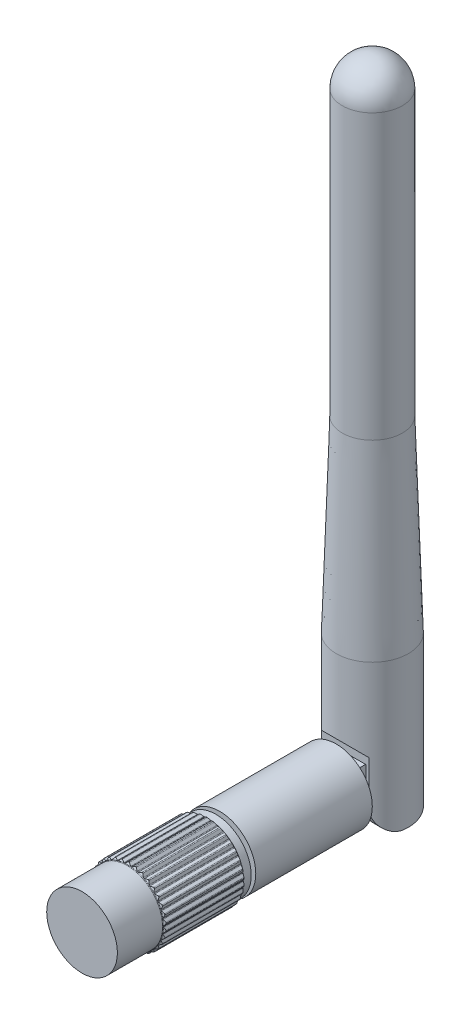
SolidWorks part; units mm, degrees
ref_plane "Front Plane" through (0, 0, 0) normal (0, 0, 1) x (1, 0, 0)
ref_plane "Top Plane" through (0, 0, 0) normal (0, 1, 0) x (1, 0, 0)
ref_plane "Right Plane" through (0, 0, 0) normal (1, 0, 0) x (0, 0, -1)
sketch "Sketch1" plane through (0, 0, 0) normal (1, 0, 0) x (0, 0, -1)
  line L0 (0, 0) -> (4.8, 0)
  line L1 (4.8, 0) -> (4.8, 20)
  line L2 (4.8, 20) -> (4, 45)
  line L3 (4, 45) -> (4, 82.7)
  line L4 (0, 0) -> (0, 86.7)
  line L5 (0, 86.7) -> (7.0365, 86.7) construction
  arc A0 (4, 82.7) -> (0, 86.7) centre (0, 82.7) ccw
  dimension "D1" = 86.7
  dimension "D2" = 4.8
  dimension "D3" = 4
  dimension "D4" = 20
  dimension "D5" = 25
revolve "Revolve1" add sketch "Sketch1" angle 360 about L4
sketch "Sketch2" plane through (0, 0, 0) normal (0, -1, 0) x (1, 0, 0)
  line L1 (-2.75, 4.8) -> (2.75, 4.8)
  line L2 (-2.75, 4.8) -> (-2.75, -3)
  line L3 (-2.75, -3) -> (2.75, -3)
  line L4 (2.75, 4.8) -> (2.75, -3)
  circle A1 centre (0, 0) radius 4.8 construction
  dimension "D1" = 5.5
  dimension "D2" = 3
  dimension "D3" = 2.75
extrude "Cut-Extrude1" cut sketch "Sketch2" against normal blind 8
sketch "Sketch4" plane through (0, 0, 0) normal (1, 0, 0) x (0, 0, -1)
  line L0 (-4.8, 10.2) -> (-3.6, 9)
  line L1 (-4.8, 20) -> (-4.8, 8) construction
  line L2 (-3.6, 9) -> (-3.6, 3)
  line L3 (-3.9341, 0) -> (4.8, 0) construction
  line L4 (-0.6, 0) -> (-4.8, 0)
  line L5 (-4.8, 0) -> (-4.8, 10.2)
  arc A0 (-3.6, 3) -> (-0.6, 0) centre (-0.6, 3) ccw
  dimension "D4" = 3
  dimension "D1" = 45
  dimension "D2" = 1.2
  dimension "D3" = 9
extrude "Cut-Extrude2" cut sketch "Sketch4" against normal up to next and the other way up to next
sketch "Sketch3" plane through (-2.75, 0, 0) normal (1, 0, 0) x (0, 0, -1)
  line L0 (-4.8, 7.7) -> (-4.8, 1.9)
  line L1 (-4.8, 1.9) -> (0, 1.9)
  line L2 (0, 7.7) -> (-4.8, 7.7)
  line L3 (-0.6, 0) -> (4.8, 0) construction
  arc A0 (0, 1.9) -> (0, 7.7) centre (0, 4.8) ccw
  dimension "D1" = 5.8
  dimension "D2" = 4.8
  dimension "D3" = 4.8
extrude "Boss-Extrude1" add sketch "Sketch3" along normal blind 4.8 from offset 0.35 separate body
sketch "Sketch5" plane through (0, 0, 4.8) normal (0, 0, 1) x (1, 0, 0)
  line L0 (2.4, 1.9) -> (-2.4, 1.9) construction
  circle A0 centre (0, 4.8) radius 4.8
  dimension "D1" = 9.6
  dimension "D2" = 2.9
extrude "Boss-Extrude2" add sketch "Sketch5" along normal blind 15.5
sketch "Sketch6" plane through (0, 0, 20.3) normal (0, 0, 1) x (1, 0, 0)
  circle A0 centre (0, 4.8) radius 3.5
  dimension "D1" = 7
extrude "Boss-Extrude3" add sketch "Sketch6" along normal blind 0.5
sketch "Sketch7" plane through (0, 0, 20.8) normal (0, 0, 1) x (1, 0, 0)
  circle A0 centre (0, 4.8) radius 4.7
  dimension "D1" = 9.4
extrude "Boss-Extrude4" add sketch "Sketch7" along normal blind 17.8
sketch "Sketch8" plane through (0, 0, 38.6) normal (0, 0, 1) x (1, 0, 0)
  line L0 (0, 4.8) -> (-0.4337, 0.12) construction
  line L1 (0, 4.8) -> (0.4337, 0.12) construction
  line L2 (-0.4337, 0.12) -> (-0.4383, 0.0703)
  line L3 (-0.366, 0.046) -> (-0.0723, -0.1758)
  line L4 (0.0723, -0.1758) -> (0.366, 0.046)
  line L5 (0.4383, 0.0703) -> (0.4337, 0.12)
  line L6 (0.4337, 0.12) -> (-0.4337, 0.12)
  line L7 (-0.4383, 0.0703) -> (0.4383, 0.0703) construction
  circle A0 centre (0, 4.8) radius 5 construction
  circle A1 centre (0, 4.8) radius 4.7 construction
  arc A2 (-0.4383, 0.0703) -> (-0.366, 0.046) centre (-0.4383, -0.0497) cw
  arc A3 (-0.0723, -0.1758) -> (0.0723, -0.1758) centre (0, -0.08) ccw
  arc A4 (0.366, 0.046) -> (0.4383, 0.0703) centre (0.4383, -0.0497) cw
  dimension "D1" = 10
  dimension "D2" = 0.12
  dimension "D3" = 0.05
  dimension "D4" = 10.588
extrude "Boss-Extrude5" add sketch "Sketch8" against normal blind 10.8 from offset 6 offset against normal yes
pattern_circular "CirPattern1" count 34 over 360 about axis through (0, 4.8, 38.6) along (0, 0, 1) of "Boss-Extrude5"
sketch "Sketch9" plane through (0, 0, 0) normal (1, 0, 0) x (0, 0, -1)
  line L0 (-32.6, 9.4058) -> (-32.6, 9.6777) construction
  line L1 (-32.5134, 9.55) -> (-32.3979, 9.75)
  line L2 (-21.8, 9.8) -> (-32.6, 9.8) construction
  line L3 (-32.6, 9.5) -> (-32.6, 9.8)
  line L4 (-32.6, 9.8) -> (-32.6, 9.7758) construction
  line L5 (-32.6, 9.8) -> (-32.3113, 9.8)
  line L6 (-21.8, 9.4058) -> (-21.8, 9.6777) construction
  line L7 (-21.8866, 9.55) -> (-22.0021, 9.75)
  line L8 (-22.0887, 9.8) -> (-21.8, 9.8)
  line L9 (-21.8, 9.7758) -> (-21.8, 9.8) construction
  line L10 (-21.8, 9.8) -> (-21.8, 9.5)
  line L11 (-21.8, 9.5) -> (-32.6, 9.5) construction
  line L12 (-20.8, 9.5) -> (-21.8, 9.5) construction
  line L13 (-20.8, 4.8) -> (-38.6, 4.8) construction
  line L14 (-20.8, 0.1) -> (-20.8, 9.5) construction
  line L15 (-38.6, 9.5) -> (-38.6, 0.1) construction
  arc A0 (-32.6, 9.5) -> (-32.5134, 9.55) centre (-32.6, 9.6) ccw
  arc A1 (-32.3979, 9.75) -> (-32.3113, 9.8) centre (-32.3113, 9.7) cw
  arc A2 (-21.8, 9.5) -> (-21.8866, 9.55) centre (-21.8, 9.6) cw
  arc A3 (-22.0021, 9.75) -> (-22.0887, 9.8) centre (-22.0887, 9.7) ccw
  dimension "D4" = 0.1
  dimension "D1" = 0.3
  dimension "D2" = 30
  dimension "D3" = 30
revolve "Cut-Revolve1" cut sketch "Sketch9" angle 360 about L13
